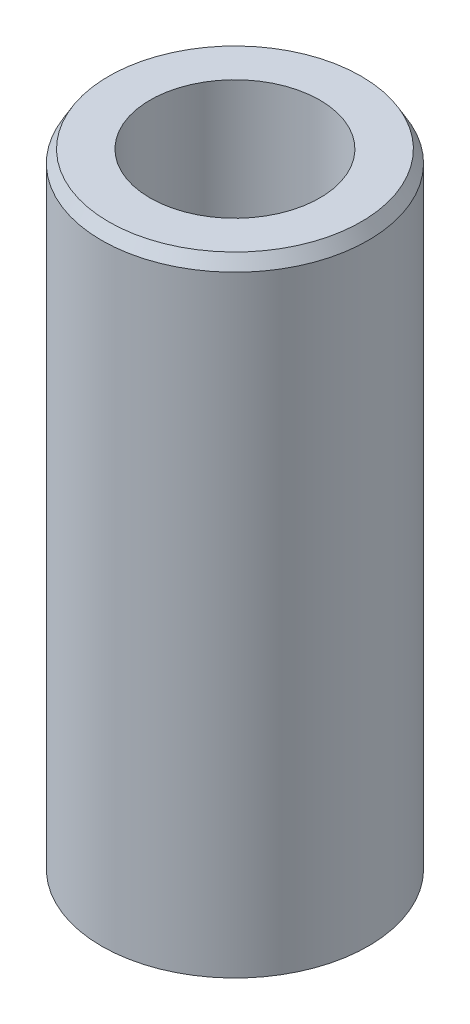
SolidWorks part; units mm, degrees
ref_plane "Front Plane" through (0, 0, 0) normal (0, 0, 1) x (1, 0, 0)
ref_plane "Top Plane" through (0, 0, 0) normal (0, 1, 0) x (1, 0, 0)
ref_plane "Right Plane" through (0, 0, 0) normal (1, 0, 0) x (0, 0, -1)
sketch "Sketch1" plane through (0, 0, 0) normal (0, 1, 0) x (1, 0, 0)
  circle A0 centre (0, 0) radius 30
  dimension "SHAFT_OD" = 60
extrude "Boss-Extrude1" add sketch "Sketch1" along normal blind 141.9017
sketch "Sketch2" plane through (0, 0, 0) normal (0, 1, 0) x (1, 0, 0)
  circle A0 centre (0, 0) radius 19.0893
  dimension "BORE_D" = 38.1785
extrude "Cut-Extrude1" cut sketch "Sketch2" along normal through all
chamfer "Chamfer1" distance 2.7963 angle 30 2 edges at (0, 141.9017, 30) (0, 0, 30) first distance on face at (0, 141.9017, 30) first distance on face at (0, 0, 19.0893)
